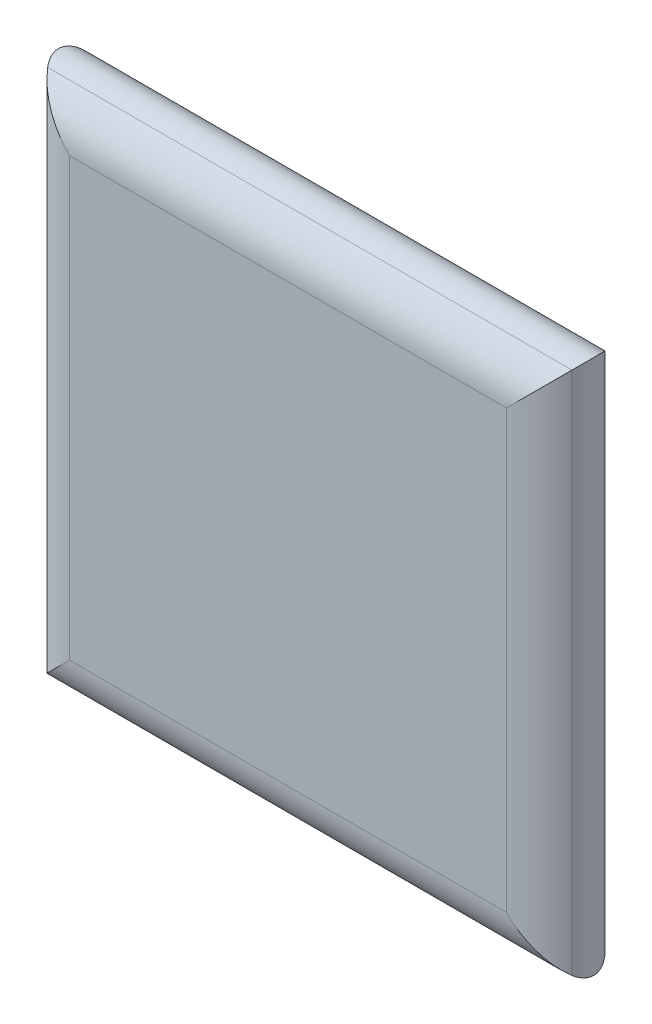
SolidWorks part; units mm, degrees
ref_plane "Front Plane" through (0, 0, 0) normal (0, 0, 1) x (1, 0, 0)
ref_plane "Top Plane" through (0, 0, 0) normal (0, 1, 0) x (1, 0, 0)
ref_plane "Right Plane" through (0, 0, 0) normal (1, 0, 0) x (0, 0, -1)
sketch "Sketch1" plane through (0, 0, 0) normal (0, 0, 1) x (1, 0, 0)
  line L0 (-238.3838, 266.6667) -> (-238.3838, -233.3333)
  line L1 (-238.3838, -233.3333) -> (261.6162, -233.3333)
  line L2 (261.6162, -233.3333) -> (261.6162, 266.6667)
  line L3 (261.6162, 266.6667) -> (-238.3838, 266.6667)
  dimension "D1" = 500
  dimension "D2" = 500
extrude "Boss-Extrude1" add sketch "Sketch1" along normal blind 60
fillet "Fillet3" radius 50 4 edges at (261.6162, 16.6667, 60) (11.6162, -233.3333, 60) (-238.3838, 16.6667, 60) (11.6162, 266.6667, 60)
fillet "Fillet4" radius 50 4 edges at (-238.3838, 16.6667, 0) (11.6162, -233.3333, 0) (261.6162, 16.6667, 0) (11.6162, 266.6667, 0)
fillet "Fillet6" radius 25 4 edges at (-238.3838, 16.6667, 10) (11.6162, -233.3333, 10) (261.6162, 16.6667, 10) (11.6162, 266.6667, 10)
